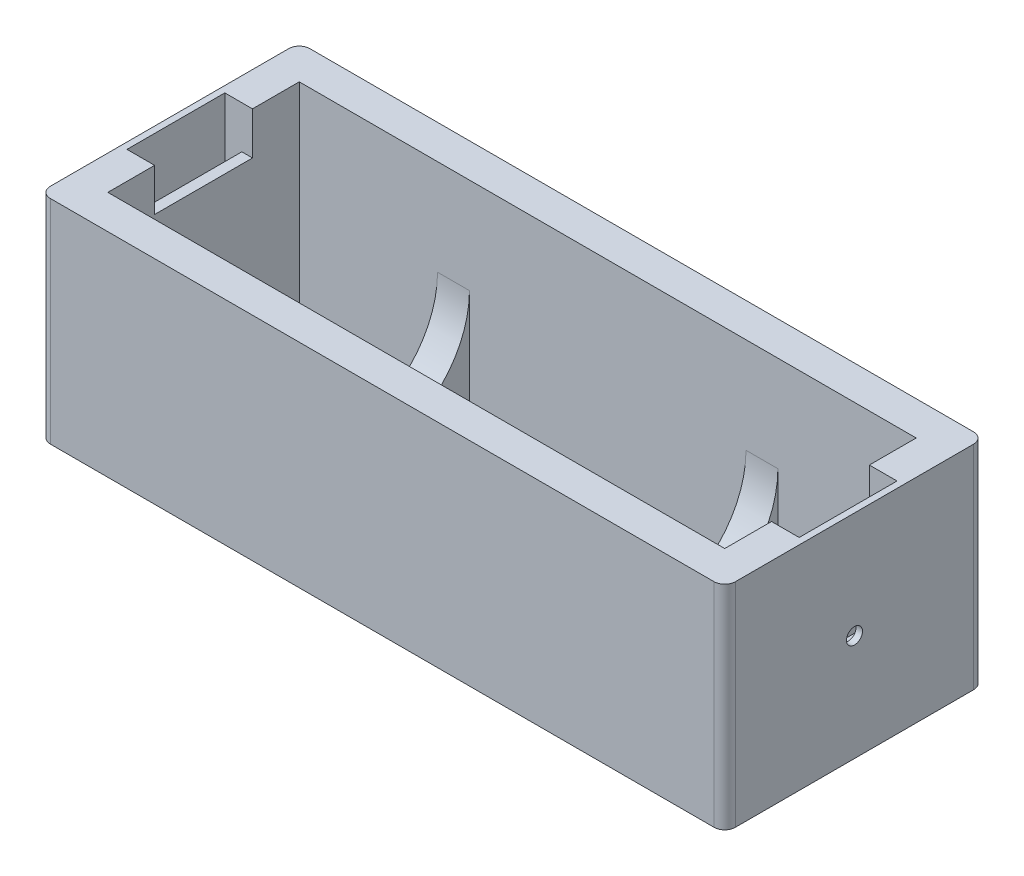
SolidWorks part; units mm, degrees
ref_plane "Front Plane" through (0, 0, 0) normal (0, 0, 1) x (1, 0, 0)
ref_plane "Top Plane" through (0, 0, 0) normal (0, 1, 0) x (1, 0, 0)
ref_plane "Right Plane" through (0, 0, 0) normal (1, 0, 0) x (0, 0, -1)
sketch "Sketch2" plane through (0, 0, 0) normal (0, 1, 0) x (1, 0, 0)
  line L1 (-32.2, -12.2) -> (32.2, -12.2)
  line L2 (-32.2, -12.2) -> (-32.2, 12.2)
  line L3 (-32.2, 12.2) -> (32.2, 12.2)
  line L4 (32.2, -12.2) -> (32.2, 12.2)
  line L5 (-32.2, -12.2) -> (32.2, 12.2) construction
  line L6 (-32.2, 12.2) -> (32.2, -12.2) construction
  point P0 (0, 0)
  dimension "D1" = 64.4
  dimension "D2" = 24.4
extrude "Boss-Extrude1" add sketch "Sketch2" along normal blind 20
sketch "Sketch3" plane through (0, 20, 0) normal (0, 1, 0) x (1, 0, 0)
  line L0 (32.2, -12.2) -> (32.2, 12.2) construction
  line L1 (-29, 9) -> (29, 9)
  line L2 (-29, 9) -> (-29, -9)
  line L3 (-29, -9) -> (29, -9)
  line L4 (29, 9) -> (29, -9)
  line L5 (-29, 9) -> (29, -9) construction
  line L6 (-29, -9) -> (29, 9) construction
  line L7 (-32.2, -12.2) -> (32.2, -12.2) construction
  point P0 (0, 0)
  dimension "D1" = 3.2
  dimension "D2" = 3.2
extrude "Cut-Extrude1" cut sketch "Sketch3" against normal offset from surface (18 mm away) 2 up to face at (0, 0, 0)
fillet "Fillet1" radius 1 4 edges at (-32.2, 10, -12.2) (32.2, 10, -12.2) (32.2, 10, 12.2) (-32.2, 10, 12.2)
sketch "Sketch4" plane through (0, 20, 0) normal (0, 1, 0) x (1, 0, 0)
  line L0 (-29, 9) -> (-29, -9) construction
  line L1 (-29, 0) -> (-30, 0)
  line L2 (-29, 0) -> (-29, 4.6)
  line L3 (-29, 4.6) -> (-30, 4.6)
  line L4 (-30, 0) -> (-30, 4.6)
  dimension "D2" = 4.6
extrude "Cut-Extrude2" cut sketch "Sketch4" against normal offset from surface (4 mm away) 4 up to face at (0, 20, 0)
sketch "Sketch5" plane through (0, 20, 0) normal (0, 1, 0) x (1, 0, 0)
  line L1 (-30, 0) -> (-31.6, 0)
  line L2 (-30, 0) -> (-30, 4.6)
  line L3 (-30, 4.6) -> (-31.6, 4.6)
  line L4 (-31.6, 0) -> (-31.6, 4.6)
  dimension "D2" = 4.6
  dimension "D1" = 1.6
extrude "Cut-Extrude3" cut sketch "Sketch5" against normal offset from surface (12 mm away) 12 up to face at (-14.75, 20, -1.15)
mirror "Mirror4" about plane through (0, 0, 0) normal (1, 0, 0) of "Cut-Extrude3", "Cut-Extrude2"
mirror "Mirror5" about plane through (0, 0, 0) normal (0, 0, 1) of "Mirror4"
sketch "Sketch6" plane through (32.2, 0, 0) normal (1, 0, 0) x (0, 0, -1)
  line L0 (-11.2, 0) -> (11.2, 0) construction
  circle A0 centre (0, 10) radius 0.75
  dimension "D1" = 1.5
  dimension "D2" = 10
extrude "Cut-Extrude4" cut sketch "Sketch6" against normal up to next
mirror "Mirror6" about plane through (0, 0, 0) normal (1, 0, 0) of "Cut-Extrude4"
ref_plane "Plane1" through (-14.5, 0, 0) normal (1, 0, 0) x (0, 0, -1)
sketch "Sketch7" plane through (-14.5, 0, 0) normal (1, 0, 0) x (0, 0, -1)
  line L0 (-9, 2) -> (9, 2) construction
  line L1 (-9, 2) -> (-9, 20) construction
  line L2 (9, 2) -> (9, 20) construction
  circle A0 centre (0, 11) radius 9
sketch "Sketch8" plane through (0, 2, 0) normal (0, 1, 0) x (1, 0, 0)
  line L0 (-14.5, -9) -> (-14.5, 9) construction
  line L1 (-16, -9) -> (-13, -9)
  line L2 (-16, -9) -> (-16, 9)
  line L3 (-16, 9) -> (-13, 9)
  line L4 (-13, -9) -> (-13, 9)
  line L5 (-16, -9) -> (-13, 9) construction
  line L6 (-16, 9) -> (-13, -9) construction
  line L7 (29, 9) -> (-29, 9) construction
  point P0 (-14.5, 0)
  dimension "D1" = 3
extrude "Boss-Extrude2" add sketch "Sketch8" along normal blind 9
extrude "Cut-Extrude5" cut sketch "Sketch7" against normal up to next and the other way up to next
mirror "Mirror7" about plane through (0, 0, 0) normal (1, 0, 0) of "Cut-Extrude5", "Boss-Extrude2"
equation "\"D1@Sketch2\"= 50 + 6.4 + 8"
equation "\"D2@Sketch2\" = 14 + 6.4 + 4"
equation "\"D1@Boss-Extrude1\"= 14 + 2 + 4"
equation "\"D1@Sketch3\"=3.2"
equation "\"D2@Sketch3\"=3.2"
equation "\"D1@Cut-Extrude1\"=2"
equation "\"D1@Fillet1\"=1"
equation "\"D2@Sketch4\"=4.6"
equation "\"D1@Sketch5\"=1.6"
equation "\"D2@Sketch5\"=4.6"
